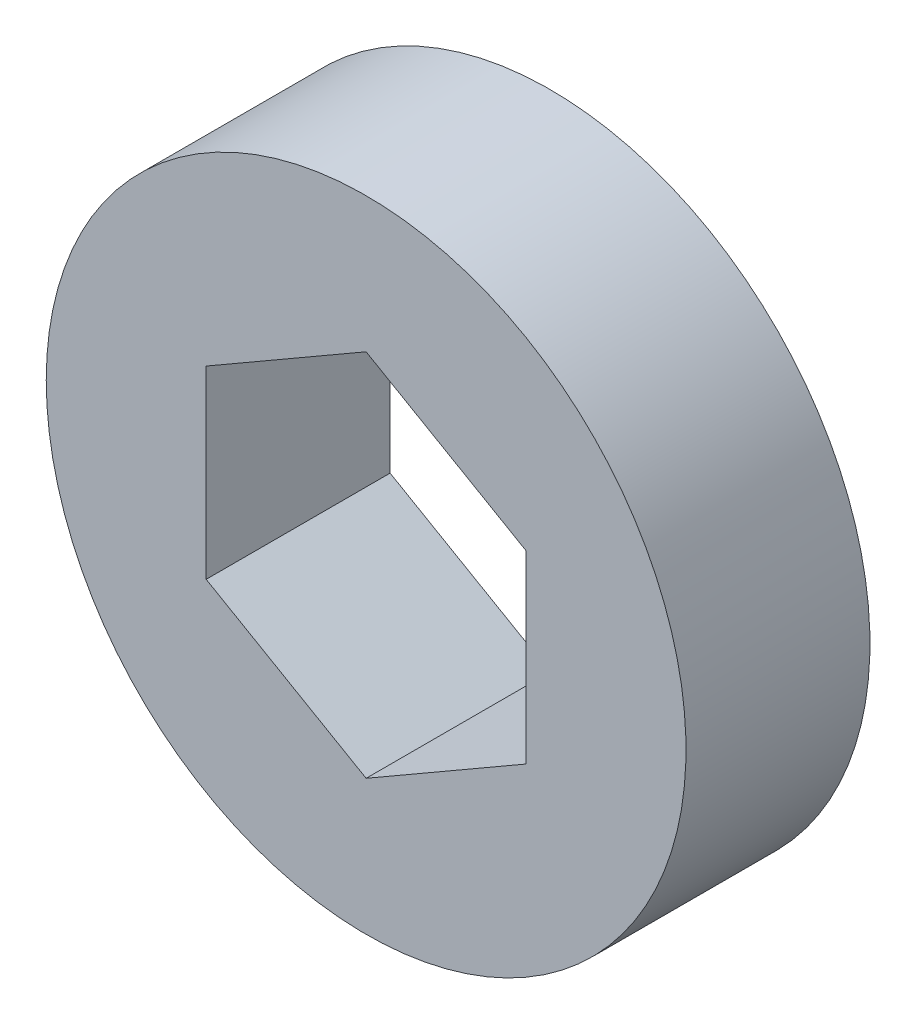
SolidWorks part; units mm, degrees
material "PET"
ref_plane "Front Plane" through (0, 0, 0) normal (0, 0, 1) x (1, 0, 0)
ref_plane "Top Plane" through (0, 0, 0) normal (0, 1, 0) x (1, 0, 0)
ref_plane "Right Plane" through (0, 0, 0) normal (1, 0, 0) x (0, 0, -1)
sketch "Sketch1" plane through (0, 0, 0) normal (0, 0, 1) x (1, 0, 0)
  line L1 (0, 7.3323) -> (-6.35, 3.6662)
  line L2 (-6.35, 3.6662) -> (-6.35, -3.6662)
  line L3 (-6.35, -3.6662) -> (0, -7.3323)
  line L4 (0, -7.3323) -> (6.35, -3.6662)
  line L5 (6.35, -3.6662) -> (6.35, 3.6662)
  line L6 (6.35, 3.6662) -> (0, 7.3323)
  circle A0 centre (0, 0) radius 6.35 construction
  circle A1 centre (0, 0) radius 12.7
  dimension "D1" = 12.7
  dimension "D2" = 25.4
extrude "Boss-Extrude1" add sketch "Sketch1" along normal mid plane 7.3025
